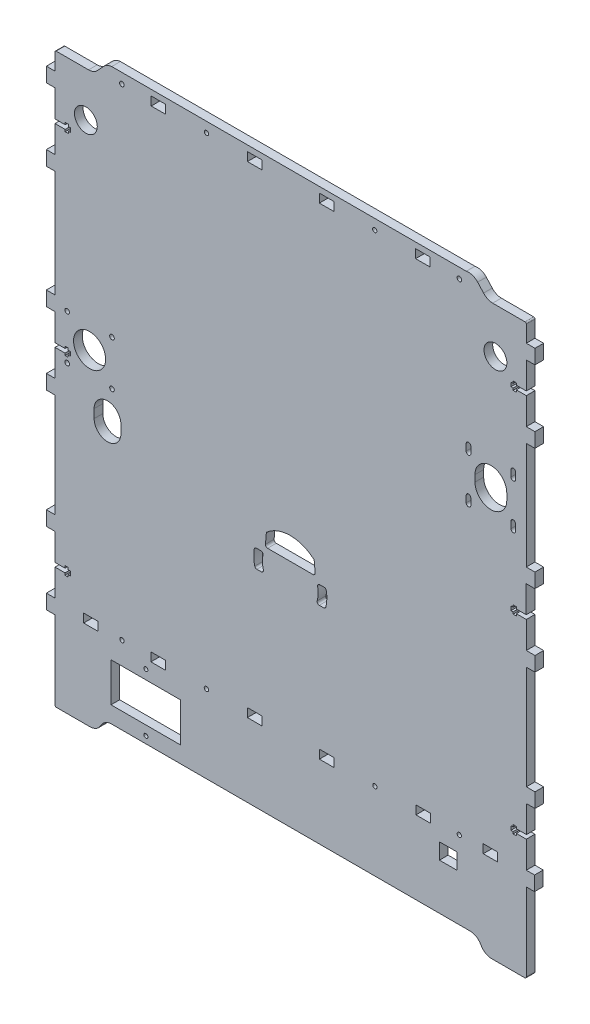
SolidWorks part; units mm, degrees
ref_plane "Спереди" through (0, 0, 0) normal (0, 0, 1) x (1, 0, 0)
ref_plane "Сверху" through (0, 0, 0) normal (0, 1, 0) x (1, 0, 0)
ref_plane "Справа" through (0, 0, 0) normal (1, 0, 0) x (0, 0, -1)
sketch "Эскиз1" plane through (0, 0, 0) normal (0, 0, 1) x (1, 0, 0)
  line L0 (-11.4163, -133.8634) -> (-21.4163, -133.8634)
  line L1 (-21.4163, -133.8634) -> (-21.4163, -127.8634)
  line L2 (-11.4163, -127.8634) -> (-11.4163, -133.8634)
  line L3 (-21.4163, -127.8634) -> (-11.4163, -127.8634)
  line L4 (-61.2563, -127.8634) -> (-61.2563, -133.8634)
  line L5 (-71.2563, -127.8634) -> (-61.2563, -127.8634)
  line L6 (-71.2563, -133.8634) -> (-71.2563, -127.8634)
  line L7 (-61.2563, -133.8634) -> (-71.2563, -133.8634)
  line L8 (61.6637, -152.8634) -> (61.6637, -141.8634)
  line L9 (61.6637, -141.8634) -> (73.7637, -141.8634)
  line L10 (73.7637, -141.8634) -> (73.7637, -152.8634)
  line L11 (73.7637, -152.8634) -> (61.6637, -152.8634)
  line L12 (-197.4876, 21.4243) -> (-197.4866, 20.0542)
  line L13 (-204.4363, 24.2766) -> (-204.4363, 42.8766)
  line L14 (-195.2876, 25.6494) -> (-195.2876, 25.6766)
  line L15 (127.7355, 42.8766) -> (127.7355, 52.8766)
  line L16 (-193.7868, 24.2485) -> (-193.7868, 24.2757)
  line L17 (-195.2868, 24.2757) -> (-195.2876, 25.6494)
  line L18 (-195.2868, 21.4269) -> (-195.2868, 21.4541)
  line L19 (-193.7868, 21.4541) -> (-193.7868, 24.2485)
  line L20 (112.6676, 24.3034) -> (112.6676, 24.2763)
  line L21 (114.8676, 24.3037) -> (114.8674, 25.6766)
  line L22 (-195.2868, 20.0542) -> (-195.2868, 21.4269)
  line L23 (111.1697, 21.5032) -> (111.1697, 21.4761)
  line L24 (111.1676, 24.2752) -> (111.1697, 21.5032)
  line L25 (121.7314, 24.2766) -> (121.7314, 42.8766)
  line L26 (-197.4876, 25.6494) -> (-197.4874, 24.2766)
  line L27 (127.7772, -7.1234) -> (127.7772, 2.8766)
  line L28 (112.6708, 20.1034) -> (112.6708, 20.0763)
  line L29 (-204.4363, 21.4566) -> (-204.4363, 21.4766)
  line L30 (121.7355, 52.8766) -> (121.7355, 127.0366)
  line L31 (-210.4363, 42.8766) -> (-210.4363, 52.8766)
  line L32 (-204.4363, 2.8766) -> (-204.4363, 21.4566)
  line L33 (-204.4363, 52.8766) -> (-204.4363, 127.0366)
  line L34 (-128.0563, -133.8634) -> (-138.0563, -133.8634)
  line L35 (-138.0563, -133.8634) -> (-138.0563, -127.8634)
  line L36 (-138.0563, -127.8634) -> (-128.0563, -127.8634)
  line L37 (-128.0563, -127.8634) -> (-128.0563, -133.8634)
  line L38 (-174.6363, -133.8634) -> (-184.6363, -133.8634)
  line L39 (-184.6363, -133.8634) -> (-184.6363, -127.8634)
  line L40 (-184.6363, -127.8634) -> (-174.6363, -127.8634)
  line L41 (-174.6363, -127.8634) -> (-174.6363, -133.8634)
  line L42 (91.9637, -133.8634) -> (101.9637, -133.8634)
  line L43 (101.9637, -133.8634) -> (101.9637, -127.8634)
  line L44 (101.9637, -127.8634) -> (91.9637, -127.8634)
  line L45 (91.9637, -127.8634) -> (91.9637, -133.8634)
  line L46 (55.3837, -133.8634) -> (45.3837, -133.8634)
  line L47 (45.3837, -133.8634) -> (45.3837, -127.8634)
  line L48 (45.3837, -127.8634) -> (55.3837, -127.8634)
  line L49 (55.3837, -127.8634) -> (55.3837, -133.8634)
  line L50 (-18.1346, -29.194) -> (-21.1843, -29.194)
  line L51 (-21.5365, -41.694) -> (-18.4403, -41.694)
  line L52 (-64.7445, -41.694) -> (-61.6484, -41.694)
  line L53 (-62.0005, -29.194) -> (-65.0502, -29.194)
  line L54 (-58.1883, -16.8245) -> (-58.7957, -23.7669)
  line L55 (-24.3892, -23.7669) -> (-24.9965, -16.8245)
  line L56 (-57.3014, -25.3976) -> (-25.8835, -25.3976)
  line L57 (-165.6924, -146.4128) -> (-165.6924, -173.4128)
  line L58 (-165.6924, -173.4128) -> (-117.6924, -173.4128)
  line L59 (-117.6924, -173.4128) -> (-117.6924, -146.4128)
  line L60 (-117.6924, -146.4128) -> (-165.6924, -146.4128)
  line L61 (-181.2137, 199.4366) -> (-203.6703, 199.4366)
  line L62 (-170.8491, 206.6945) -> (-174.9446, 202.2149)
  line L63 (127.478, -128.8434) -> (121.7637, -128.8434)
  line L64 (80.2335, 209.4366) -> (-165.1973, 209.4366)
  line L65 (121.7772, -7.1234) -> (127.7772, -7.1234)
  line L66 (88.0955, 206.8296) -> (92.1957, 202.3542)
  line L67 (98.4674, 199.4366) -> (120.8437, 199.4366)
  line L68 (121.7637, 187.0366) -> (121.7637, 198.5166)
  line L69 (121.7637, 177.0366) -> (127.7637, 177.0366)
  line L70 (127.7637, 177.0366) -> (127.7637, 187.0366)
  line L71 (-204.4363, 42.8766) -> (-210.4363, 42.8766)
  line L72 (120.8067, -193.8634) -> (97.8063, -193.8634)
  line L73 (91.3771, -190.805) -> (89.3204, -187.7854)
  line L74 (-203.3585, -193.8634) -> (-180.2324, -193.8634)
  line L75 (-210.4363, 177.0366) -> (-210.4363, 187.0366)
  line L76 (114.8517, 158.4366) -> (114.8517, 159.8367)
  line L77 (121.8652, -107.4334) -> (114.8652, -107.4334)
  line L78 (-204.4363, 158.4366) -> (-204.4363, 177.0366)
  line L79 (114.8652, -106.0333) -> (112.6643, -106.0333)
  line L80 (-204.4363, -107.4334) -> (-204.4363, -88.8534)
  line L81 (114.8709, -110.2334) -> (121.7637, -110.2334)
  line L82 (121.8652, -107.4334) -> (121.8652, -88.8534)
  line L83 (111.1668, -110.2331) -> (112.6668, -110.2322)
  line L84 (112.6643, -106.0333) -> (112.6652, -107.4331)
  line L85 (111.1652, -107.434) -> (111.1668, -110.2331)
  line L86 (-197.5237, -111.681) -> (-195.335, -111.6794)
  line L87 (121.7637, 158.4366) -> (114.8517, 158.4366)
  line L88 (114.8708, -111.6332) -> (114.8709, -110.2334)
  line L89 (114.8652, -107.4334) -> (114.8652, -106.0333)
  line L90 (112.6652, -107.4331) -> (111.1652, -107.434)
  line L91 (112.6533, 155.6378) -> (112.6541, 154.2369)
  line L92 (-197.4908, -105.897) -> (-197.4906, -107.4334)
  line L93 (-204.4363, 21.4766) -> (-197.4876, 21.4766)
  line L94 (-197.4876, 21.4766) -> (-197.4876, 21.4243)
  line L95 (-204.4363, 155.6366) -> (-197.3871, 155.6366)
  line L96 (121.7637, -128.8434) -> (121.7637, -110.2334)
  line L97 (121.7801, 2.8766) -> (121.7801, 21.4766)
  line L98 (127.478, -138.8434) -> (127.478, -128.8434)
  line L99 (114.8706, 21.4766) -> (121.7801, 21.4766)
  line L100 (-197.3871, 155.6366) -> (-197.3871, 154.2365)
  line L101 (-197.4181, 158.4366) -> (-204.4363, 158.4366)
  line L102 (-195.2181, 158.419) -> (-195.2181, 159.8366)
  line L103 (112.6668, -110.2322) -> (112.6676, -111.6331)
  line L104 (-197.4906, -107.4334) -> (-204.4363, -107.4334)
  line L105 (112.6508, 159.8367) -> (112.6517, 158.4369)
  line L106 (114.8541, 154.2368) -> (114.8542, 155.6366)
  line L107 (-197.5239, -110.2334) -> (-197.5237, -111.681)
  line L108 (111.1517, 158.436) -> (111.1533, 155.6369)
  line L109 (-195.2876, 25.6766) -> (-197.4876, 25.6766)
  line L110 (112.6708, 20.0763) -> (114.8708, 20.0766)
  line L111 (112.6541, 154.2369) -> (114.8541, 154.2368)
  line L112 (111.1533, 155.6369) -> (112.6533, 155.6378)
  line L113 (121.7772, -78.8534) -> (121.7772, -7.1234)
  line L114 (-195.1863, 155.619) -> (-193.7155, 155.619)
  line L115 (112.6666, 25.6762) -> (112.6676, 24.3034)
  line L116 (114.8676, 24.2766) -> (114.8676, 24.3037)
  line L117 (112.6517, 158.4369) -> (111.1517, 158.436)
  line L118 (-195.3299, -105.8955) -> (-197.4908, -105.897)
  line L119 (-193.6779, -110.2778) -> (-193.6833, -107.2844)
  line L120 (-195.3368, -110.2798) -> (-193.6779, -110.2778)
  line L121 (-197.4866, 20.0542) -> (-195.2868, 20.0542)
  line L122 (-195.2868, 21.4541) -> (-193.7868, 21.4541)
  line L123 (114.8708, 20.0766) -> (114.8708, 20.1037)
  line L124 (-204.4363, -110.2334) -> (-197.5239, -110.2334)
  line L125 (-195.3281, -107.2865) -> (-195.3299, -105.8955)
  line L126 (-193.7868, 24.2757) -> (-195.2868, 24.2757)
  line L127 (-197.3871, 154.2365) -> (-195.1863, 154.2365)
  line L128 (-195.335, -111.6794) -> (-195.3368, -110.2798)
  line L129 (-197.4181, 159.8366) -> (-197.4181, 158.4366)
  line L130 (-193.6833, -107.2844) -> (-195.3281, -107.2865)
  line L131 (-195.1863, 154.2365) -> (-195.1863, 155.619)
  line L133 (114.8517, 159.8367) -> (112.6508, 159.8367)
  line L134 (-193.7155, 155.619) -> (-193.7155, 158.419)
  line L135 (114.8542, 155.6366) -> (121.7637, 155.6366)
  line L136 (-197.4874, 24.2766) -> (-204.4363, 24.2766)
  line L137 (114.8708, 20.1037) -> (114.8706, 21.4766)
  line L138 (-197.4876, 25.6766) -> (-197.4876, 25.6494)
  line L139 (112.6676, -111.6331) -> (114.8708, -111.6332)
  line L140 (112.6676, 24.2763) -> (111.1676, 24.2752)
  line L141 (-195.2181, 159.8366) -> (-197.4181, 159.8366)
  line L142 (121.7637, 158.4366) -> (121.7637, 177.0366)
  line L143 (114.8674, 25.6766) -> (112.6666, 25.6762)
  line L144 (-193.7155, 158.419) -> (-195.2181, 158.419)
  line L145 (-204.4363, -7.1234) -> (-210.4363, -7.1234)
  line L146 (-204.4363, 177.0366) -> (-210.4363, 177.0366)
  line L147 (127.7772, -88.8534) -> (127.7772, -78.8534)
  line L148 (111.1697, 21.4761) -> (112.6697, 21.4772)
  line L149 (121.7314, 24.2766) -> (114.8676, 24.2766)
  line L150 (112.6697, 21.4772) -> (112.6708, 20.1034)
  line L151 (-204.4363, -192.8001) -> (-204.4363, -138.8434)
  line L152 (-204.4363, 137.0366) -> (-204.4363, 155.6366)
  line L153 (-210.4363, 127.0366) -> (-210.4363, 137.0366)
  line L154 (-204.4363, 127.0366) -> (-210.4363, 127.0366)
  line L155 (127.7355, 127.0366) -> (127.7355, 137.0366)
  line L156 (127.7355, 137.0366) -> (121.7637, 137.0366)
  line L157 (-137.8416, 205.4366) -> (-127.8416, 205.4366)
  line L158 (-127.8416, 205.4366) -> (-127.8416, 199.4366)
  line L159 (-127.8416, 199.4366) -> (-137.8416, 199.4366)
  line L160 (-137.8416, 199.4366) -> (-137.8416, 205.4366)
  line L161 (55.1584, 199.4366) -> (45.1584, 199.4366)
  line L162 (45.1584, 199.4366) -> (45.1584, 205.4366)
  line L163 (45.1584, 205.4366) -> (55.1584, 205.4366)
  line L164 (55.1584, 205.4366) -> (55.1584, 199.4366)
  line L165 (-61.2416, 199.4366) -> (-71.2416, 199.4366)
  line L166 (-71.2416, 199.4366) -> (-71.2416, 205.4366)
  line L167 (-71.2416, 205.4366) -> (-61.2416, 205.4366)
  line L169 (-11.4416, 199.4366) -> (-21.4416, 199.4366)
  line L170 (-21.4416, 199.4366) -> (-21.4416, 205.4366)
  line L171 (-21.4416, 205.4366) -> (-11.4416, 205.4366)
  line L173 (127.7637, 187.0366) -> (121.7637, 187.0366)
  line L174 (121.7637, 137.0366) -> (121.7637, 155.6366)
  line L175 (121.7355, 127.0366) -> (127.7355, 127.0366)
  line L176 (-210.4363, 2.8766) -> (-204.4363, 2.8766)
  line L177 (-204.4363, -128.8434) -> (-204.4363, -110.2334)
  line L178 (-204.4363, -78.8534) -> (-204.4363, -7.1234)
  line L179 (-210.4311, -128.8434) -> (-204.4363, -128.8434)
  line L180 (-210.4363, -88.8534) -> (-210.4363, -78.8534)
  line L181 (-210.4363, -7.1234) -> (-210.4363, 2.8766)
  line L182 (-210.4363, -78.8534) -> (-204.4363, -78.8534)
  line L183 (-173.7242, -190.8095) -> (-171.6691, -187.7888)
  line L184 (127.7355, 52.8766) -> (121.7355, 52.8766)
  line L185 (121.7637, -192.6916) -> (121.7637, -138.8434)
  line L186 (-165.1593, -184.7491) -> (82.809, -184.7491)
  line L187 (-210.4311, -138.8434) -> (-210.4311, -128.8434)
  line L188 (-204.4363, -138.8434) -> (-210.4311, -138.8434)
  line L189 (-210.4363, 137.0366) -> (-204.4363, 137.0366)
  line L190 (-210.4363, 187.0366) -> (-204.4363, 187.0366)
  line L191 (-210.4363, 52.8766) -> (-204.4363, 52.8766)
  line L192 (-204.4363, -88.8534) -> (-210.4363, -88.8534)
  line L193 (121.7637, -138.8434) -> (127.478, -138.8434)
  line L194 (127.7772, -78.8534) -> (121.7772, -78.8534)
  line L195 (127.7772, 2.8766) -> (121.7801, 2.8766)
  line L196 (-204.4363, 187.0366) -> (-204.4363, 198.2588)
  line L197 (121.7314, 42.8766) -> (127.7355, 42.8766)
  line L198 (121.8652, -88.8534) -> (127.7772, -88.8534)
  line L199 (-158.8564, -7.694) -> (-158.8564, -1.694)
  line L200 (86.2572, 90.556) -> (86.2572, 86.056)
  line L201 (111.1572, 75.056) -> (111.1572, 70.556)
  line L202 (108.2572, 86.056) -> (108.2572, 90.556)
  line L203 (114.3572, 101.556) -> (114.3572, 106.056)
  line L204 (111.1572, 106.056) -> (111.1572, 101.556)
  line L205 (114.3572, 70.556) -> (114.3572, 75.056)
  line L206 (80.1572, 75.056) -> (80.1572, 70.556)
  line L207 (83.3572, 70.556) -> (83.3572, 75.056)
  line L208 (83.3572, 101.556) -> (83.3572, 106.056)
  line L209 (-177.3564, -1.694) -> (-177.3564, -7.694)
  line L210 (80.1572, 106.056) -> (80.1572, 101.556)
  line L211 (-61.2416, 205.4366) -> (-61.2416, 199.4366)
  line L212 (-11.4416, 199.4366) -> (-11.4416, 205.4366)
  line L213 (-141.5552, -189.1404) -> (-141.5552, -133.1187) construction
  line L214 (-195.203, -133.8634) -> (114.843, -133.8634) construction
  line L215 (-204.4363, 213.0066) -> (-204.4363, -217.9418) construction
  line L216 (121.7637, 210.9354) -> (121.7637, -201.1521) construction
  arc A0 (80.1572, 70.556) -> (83.3572, 70.556) centre (81.7572, 70.556) ccw
  arc A1 (80.1572, 101.556) -> (83.3572, 101.556) centre (81.7572, 101.556) ccw
  circle A2 centre (-183.0863, 168.4366) radius 7.9
  circle A3 centre (100.4084, 168.4366) radius 7.9
  arc A4 (-16.6559, -30.4419) -> (-18.1346, -29.194) centre (-18.1346, -30.694) ccw
  arc A5 (-21.1843, -29.194) -> (-22.6563, -30.9825) centre (-21.1843, -30.694) ccw
  arc A6 (-22.9831, -39.7973) -> (-22.6563, -30.9825) centre (-41.5924, -34.694) ccw
  arc A7 (-22.9831, -39.7973) -> (-21.5365, -41.694) centre (-21.5365, -40.194) ccw
  arc A8 (-65.0502, -29.194) -> (-66.5289, -30.4419) centre (-65.0502, -30.694) ccw
  arc A9 (-66.5289, -30.4419) -> (-66.2039, -40.5407) centre (-41.5924, -34.694) ccw
  arc A10 (-66.2039, -40.5407) -> (-64.7445, -41.694) centre (-64.7445, -40.194) ccw
  arc A11 (-61.6484, -41.694) -> (-60.2018, -39.7973) centre (-61.6484, -40.194) ccw
  arc A12 (-60.5285, -30.9825) -> (-60.2018, -39.7973) centre (-41.5924, -34.694) ccw
  arc A13 (-60.5285, -30.9825) -> (-62.0005, -29.194) centre (-62.0005, -30.694) ccw
  arc A14 (-16.9809, -40.5407) -> (-16.6559, -30.4419) centre (-41.5924, -34.694) ccw
  arc A15 (-18.4403, -41.694) -> (-16.9809, -40.5407) centre (-18.4403, -40.194) ccw
  arc A16 (-57.6664, -15.8131) -> (-58.1883, -16.8245) centre (-56.694, -16.9552) ccw
  arc A17 (-25.5185, -15.8131) -> (-57.6664, -15.8131) centre (-41.5924, -34.694) ccw
  arc A18 (-24.9965, -16.8245) -> (-25.5185, -15.8131) centre (-26.4908, -16.9552) ccw
  arc A19 (-25.8835, -25.3976) -> (-24.3892, -23.7669) centre (-25.8835, -23.8976) ccw
  arc A20 (-58.7957, -23.7669) -> (-57.3014, -25.3976) centre (-57.3014, -23.8976) ccw
  circle A21 centre (-158.1416, 202.4366) radius 1.6
  arc A22 (-203.6703, 199.4366) -> (-204.4363, 198.2588) centre (-203.5603, 198.5271) ccw
  arc A23 (-181.2137, 199.4366) -> (-174.9446, 202.2149) centre (-181.2321, 207.9403) ccw
  arc A24 (-165.1973, 209.4366) -> (-170.8491, 206.6945) centre (-164.5754, 200.9594) ccw
  circle A25 centre (75.4584, 202.4366) radius 1.6
  arc A26 (88.0955, 206.8296) -> (80.2335, 209.4366) centre (81.8282, 201.0876) ccw
  arc A27 (-180.2324, -193.8634) -> (-173.7242, -190.8095) centre (-180.2521, -185.3595) ccw
  arc A28 (120.8067, -193.8634) -> (121.7637, -192.6916) centre (120.6617, -192.7683) ccw
  arc A29 (-165.1593, -184.7491) -> (-171.6691, -187.7888) centre (-165.1549, -193.2491) ccw
  arc A30 (-204.4363, -192.8001) -> (-203.3585, -193.8634) centre (-203.4855, -192.9141) ccw
  arc A31 (89.3204, -187.7854) -> (82.809, -184.7491) centre (82.809, -193.2491) ccw
  arc A32 (91.3771, -190.805) -> (97.8063, -193.8634) centre (97.8839, -185.4133) ccw
  arc A34 (92.1957, 202.3542) -> (98.4674, 199.4366) centre (98.6272, 207.9796) ccw
  circle A35 centre (16.8584, 202.4366) radius 1.5
  circle A36 centre (-99.5416, 202.4366) radius 1.5
  circle A37 centre (-196.0064, 47.306) radius 1.6
  arc A38 (-177.3564, -7.694) -> (-158.8564, -7.694) centre (-168.1064, -7.694) ccw
  circle A39 centre (-165.0064, 16.306) radius 1.6
  circle A40 centre (-196.0064, 16.306) radius 1.6
  arc A41 (86.2572, 86.056) -> (108.2572, 86.056) centre (97.2572, 86.056) ccw
  arc A42 (108.2572, 90.556) -> (86.2572, 90.556) centre (97.2572, 90.556) ccw
  arc A43 (114.3572, 75.056) -> (111.1572, 75.056) centre (112.7572, 75.056) ccw
  circle A44 centre (-180.5064, 31.806) radius 11.1
  circle A45 centre (-165.0064, 47.306) radius 1.6
  arc A46 (114.3572, 106.056) -> (111.1572, 106.056) centre (112.7572, 106.056) ccw
  arc A47 (111.1572, 101.556) -> (114.3572, 101.556) centre (112.7572, 101.556) ccw
  arc A48 (111.1572, 70.556) -> (114.3572, 70.556) centre (112.7572, 70.556) ccw
  arc A49 (83.3572, 75.056) -> (80.1572, 75.056) centre (81.7572, 75.056) ccw
  arc A50 (-158.8564, -1.694) -> (-177.3564, -1.694) centre (-168.1064, -1.694) ccw
  arc A51 (83.3572, 106.056) -> (80.1572, 106.056) centre (81.7572, 106.056) ccw
  circle A52 centre (75.3837, -130.8634) radius 1.5
  circle A53 centre (16.9837, -130.8634) radius 1.5
  circle A54 centre (-99.6563, -130.8634) radius 1.5
  circle A55 centre (-158.0563, -130.8634) radius 1.5
  arc A57 (121.7637, 198.5166) -> (120.8437, 199.4366) centre (120.8437, 198.5166) ccw
  circle A58 centre (-141.5552, -179.9491) radius 1.4
  circle A59 centre (-141.5552, -139.9491) radius 1.4
  point P319 (-207.4363, 187.0366)
  point P322 (-11.4416, 202.4366)
  point P330 (-21.4163, -130.8634)
  point P331 (55.3837, -130.8634)
  dimension "D1" = 15.8
  dimension "D2" = 15.8
  dimension "D3" = 22.2
  dimension "D6" = 19.8
  dimension "D35" = 12.1
  dimension "D38" = 48
  dimension "D96" = 2.8
  dimension "D97" = 2.8
  dimension "D4" = 403.3
  dimension "D7" = 326.2
  dimension "D10" = 12.4
  dimension "D11" = 10
  dimension "D13" = 6
  dimension "D14" = 19.8
  dimension "D15" = 4
  dimension "D16" = 7
  dimension "D17" = 7
  dimension "D18" = 4
  dimension "D19" = 4
  dimension "D20" = 7
  dimension "D21" = 7
  dimension "D22" = 4
  dimension "D23" = 6
  dimension "D24" = 28.3
  dimension "D25" = 28.3
  dimension "D26" = 28.3
  dimension "D27" = 39.84
  dimension "D28" = 10
  dimension "D29" = 10
  dimension "D30" = 10
  dimension "D31" = 10
  dimension "D32" = 11
  dimension "D33" = 21.35
  dimension "D34" = 41
  dimension "D36" = 6
  dimension "D37" = 6
  dimension "D39" = 28.3
  dimension "D41" = 31
  dimension "D45" = 18.6
  dimension "D47" = 2.8
  dimension "D48" = 18.6
  dimension "D50" = 10
  dimension "D57" = 31
  dimension "D58" = 31
  dimension "D83" = 71.73
  dimension "D84" = 10
  dimension "D85" = 6
  dimension "D88" = 6
  dimension "D89" = 18.58
  dimension "D90" = 2.8
  dimension "D98" = 4.8
  dimension "D99" = 44.8
  dimension "D100" = 60
  dimension "D101" = 6
  dimension "D102" = 10
  dimension "D103" = 3
  dimension "D104" = 6
  dimension "D105" = 10
  dimension "D106" = 3
  dimension "D107" = 6
  dimension "D108" = 10
  dimension "D109" = 6
  dimension "D110" = 10
  dimension "D111" = 3
  dimension "D112" = 6
  dimension "D113" = 10
  dimension "D114" = 3
  dimension "D115" = 6
  dimension "D116" = 10
  dimension "D118" = 16.58
  dimension "D119" = 20
  dimension "D120" = 28.4
  dimension "D121" = 28.4
  dimension "D123" = 16.58
  dimension "D124" = 20
  dimension "D125" = 28.4
  dimension "D126" = 28.4
extrude "Бобышка-Вытянуть1" add sketch "Эскиз1" along normal blind 6
